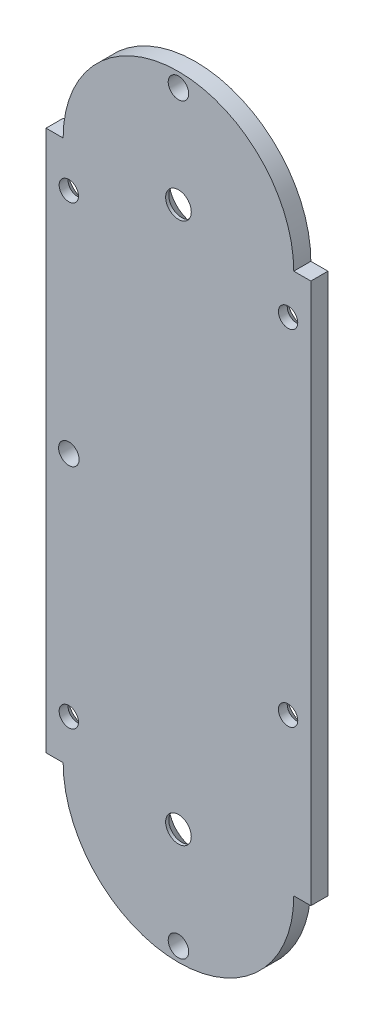
SolidWorks part; units mm, degrees
ref_plane "Front Plane" through (0, 0, 0) normal (0, 0, 1) x (1, 0, 0)
ref_plane "Top Plane" through (0, 0, 0) normal (0, 1, 0) x (1, 0, 0)
ref_plane "Right Plane" through (0, 0, 0) normal (1, 0, 0) x (0, 0, -1)
sketch "Schizzo1" plane through (0, 0, 0) normal (0, 0, 1) x (1, 0, 0)
  line L18 (0, -47.5) -> (0, 47.5) construction
  line L19 (-20.25, -47.5) -> (-20.25, 47.5) construction
  line L20 (20.25, -47.5) -> (20.25, 47.5) construction
  line L21 (20.25, -47.5) -> (23.25, -47.5)
  line L22 (23.25, -47.5) -> (-23.25, -47.5) construction
  line L23 (23.25, -47.5) -> (23.25, 47.5) construction
  line L24 (23.25, 47.5) -> (-23.25, 47.5) construction
  line L25 (-23.25, -47.5) -> (-23.25, 47.5) construction
  line L26 (23.25, -47.5) -> (-23.25, 47.5) construction
  line L27 (23.25, 47.5) -> (-23.25, -47.5) construction
  line L28 (23.25, -47.5) -> (23.25, 47.5)
  line L29 (23.25, 47.5) -> (20.25, 47.5)
  line L30 (-20.25, 47.5) -> (-23.25, 47.5)
  line L31 (-23.25, 47.5) -> (-23.25, -47.5)
  line L32 (-23.25, -47.5) -> (-20.25, -47.5)
  arc A14 (-20.25, -47.5) -> (20.25, -47.5) centre (0, -47.5) ccw construction
  arc A15 (20.25, 47.5) -> (-20.25, 47.5) centre (0, 47.5) ccw construction
  arc A16 (-20.25, 47.5) -> (20.25, 47.5) centre (0, 47.5) cw
  arc A17 (-20.25, -47.5) -> (20.25, -47.5) centre (0, -47.5) ccw
  point P2 (0, 0)
  point P8 (0, 0)
  dimension "D3" = 46.5
  dimension "D2" = 95
  dimension "D1" = 20.25
  dimension "D4" = 95
extrude "Estrusione-Estrusione1" add sketch "Schizzo1" along normal blind 3
hole_wizard "Foro svasato per Vite M4-1" positions "Schizzo4" profile "Schizzo5" countersink size "M4" standard "ISO" end condition up to next
sketch "Schizzo4" plane through (0, 0, 0) normal (0, 0, 1) x (1, 0, 0)
  point P0 (0, 47.5)
  point P3 (0, -47.5)
sketch "Schizzo5" plane through (0, 47.5, 0) normal (1, 0, 0) x (0, 1, 0)
  line L0 (0, 0) -> (0, 3)
  line L1 (0, 3) -> (2.25, 3)
  line L2 (2.25, 3) -> (2.25, 2.45)
  line L3 (2.25, 2.45) -> (4.7, 0)
  line L5 (4.7, 0) -> (0, 0)
  line L6 (-2.25, 2.45) -> (-4.7, 0) construction
  line L11 (0, -6.35) -> (0, 107.95) construction
  dimension "Thru Hole Dia." = 4.5
  dimension "Thru Hole Depth" = 3
  dimension "Near C'Sink Dia." = 9.4
  dimension "Near C'Sink Angle" = 90
hole_wizard "Foro svasato per Vite M3-1" positions "Schizzo7" profile "Schizzo8" countersink size "M3" standard "ISO" end condition up to next
sketch "Schizzo7" plane through (0, 0, 0) normal (0, 0, -1) x (-1, 0, 0)
  line L1 (23.25, 47.5) -> (23.25, -47.5) construction
  line L2 (20.25, 47.5) -> (23.25, 47.5) construction
  line L3 (23.25, -47.5) -> (20.25, -47.5) construction
  line L5 (-23.25, 47.5) -> (-20.25, 47.5) construction
  line L6 (-23.25, -47.5) -> (-23.25, 47.5) construction
  line L7 (-20.25, -47.5) -> (-23.25, -47.5) construction
  point P0 (-19.25, 40)
  point P2 (-19.25, -20.5)
  point P4 (19.25, -40)
  point P6 (19.25, 40)
  dimension "D1" = 4
  dimension "D2" = 7.5
  dimension "D3" = 7.5
  dimension "D4" = 7.5
  dimension "D5" = 4
  dimension "D6" = 27
sketch "Schizzo8" plane through (19.25, 40, 0) normal (1, 0, 0) x (0, 1, 0)
  line L0 (0, 0) -> (0, 3)
  line L1 (0, 3) -> (1.7, 3)
  line L2 (1.7, 3) -> (1.7, 1.45)
  line L3 (1.7, 1.45) -> (3.15, 0)
  line L5 (3.15, 0) -> (0, 0)
  line L6 (-1.7, 1.45) -> (-3.15, 0) construction
  line L11 (0, -6.35) -> (0, 107.95) construction
  dimension "Thru Hole Dia." = 3.4
  dimension "Thru Hole Depth" = 3
  dimension "Near C'Sink Dia." = 6.3
  dimension "Near C'Sink Angle" = 90
hole_wizard "M3 Clearance Hole1" positions "Sketch1" profile "Sketch2" hole size "M3" standard "ANSI Metric"
sketch "Sketch1" plane through (0, 0, 0) normal (0, 0, -1) x (-1, 0, 0)
  circle A0 centre (19.25, 0) radius 1.25 construction
  point P1 (19.25, 0)
  point P7 (0, 65.25)
  point P10 (0, -65.25)
sketch "Sketch2" plane through (-19.25, 0, 0) normal (1, 0, 0) x (0, 1, 0)
  line L0 (0, 0) -> (0, 5.0815)
  line L1 (0, 5.0815) -> (1.8, 4)
  line L2 (1.8, 4) -> (1.8, 0)
  line L5 (1.8, 0) -> (0, 0)
  line L10 (0, 5.0815) -> (-1.8, 4) construction
  line L11 (0, -6.35) -> (0, 107.95) construction
  dimension "Hole Dia." = 3.6
  dimension "Hole Depth" = 4
  dimension "Drill Angle" = 118
